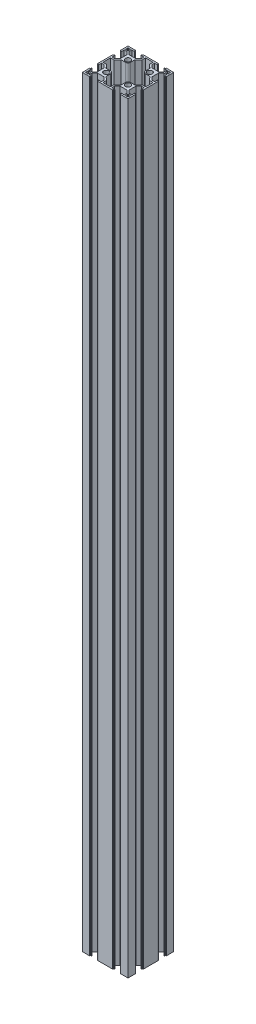
SolidWorks part; units mm, degrees
ref_plane "Front Plane" through (0, 0, 0) normal (0, 0, 1) x (1, 0, 0)
ref_plane "Top Plane" through (0, 0, 0) normal (0, 1, 0) x (1, 0, 0)
ref_plane "Right Plane" through (0, 0, 0) normal (1, 0, 0) x (0, 0, -1)
sketch "Sketch1" plane through (0, 0, 0) normal (0, 1, 0) x (1, 0, 0)
  line L0 (0, 30) -> (0, -30) construction
  line L1 (-30, -30) -> (30, -30)
  line L2 (-30, -30) -> (-30, 30)
  line L3 (-30, 30) -> (30, 30)
  line L4 (30, -30) -> (30, 30)
  line L5 (-30, -30) -> (30, 30) construction
  line L6 (-30, 30) -> (30, -30) construction
  line L7 (-30, 0) -> (30, 0) construction
  line L8 (-23.05, -28) -> (-6.95, -28)
  line L9 (-6.95, -28) -> (-6.95, -24.4)
  line L10 (-6.95, -24.4) -> (-10.615, -20.8)
  line L11 (-10.615, -20.8) -> (-19.385, -20.8)
  line L12 (-19.385, -20.8) -> (-23.05, -24.4)
  line L13 (-23.05, -24.4) -> (-23.05, -28)
  line L14 (10.615, -20.8) -> (19.385, -20.8)
  line L15 (6.95, -24.4) -> (10.615, -20.8)
  line L16 (6.95, -28) -> (6.95, -24.4)
  line L17 (23.05, -28) -> (6.95, -28)
  line L18 (23.05, -24.4) -> (23.05, -28)
  line L19 (19.385, -20.8) -> (23.05, -24.4)
  line L20 (19.385, 20.8) -> (23.05, 24.4)
  line L21 (23.05, 24.4) -> (23.05, 28)
  line L22 (23.05, 28) -> (6.95, 28)
  line L23 (6.95, 28) -> (6.95, 24.4)
  line L24 (6.95, 24.4) -> (10.615, 20.8)
  line L25 (10.615, 20.8) -> (19.385, 20.8)
  line L26 (-23.05, 24.4) -> (-23.05, 28)
  line L27 (-19.385, 20.8) -> (-23.05, 24.4)
  line L28 (-10.615, 20.8) -> (-19.385, 20.8)
  line L29 (-6.95, 24.4) -> (-10.615, 20.8)
  line L30 (-6.95, 28) -> (-6.95, 24.4)
  line L31 (-23.05, 28) -> (-6.95, 28)
  line L32 (-20.8, 19.385) -> (-24.4, 23.05)
  line L33 (-24.4, 23.05) -> (-28, 23.05)
  line L34 (-28, 23.05) -> (-28, 6.95)
  line L35 (-28, 6.95) -> (-24.4, 6.95)
  line L36 (-24.4, 6.95) -> (-20.8, 10.615)
  line L37 (-20.8, 10.615) -> (-20.8, 19.385)
  line L38 (-24.4, -23.05) -> (-28, -23.05)
  line L39 (-20.8, -19.385) -> (-24.4, -23.05)
  line L40 (-20.8, -10.615) -> (-20.8, -19.385)
  line L41 (-24.4, -6.95) -> (-20.8, -10.615)
  line L42 (-28, -6.95) -> (-24.4, -6.95)
  line L43 (-28, -23.05) -> (-28, -6.95)
  line L44 (20.8, -19.385) -> (24.4, -23.05)
  line L45 (24.4, -23.05) -> (28, -23.05)
  line L46 (28, -23.05) -> (28, -6.95)
  line L47 (28, -6.95) -> (24.4, -6.95)
  line L48 (24.4, -6.95) -> (20.8, -10.615)
  line L49 (20.8, -10.615) -> (20.8, -19.385)
  line L50 (24.4, 23.05) -> (28, 23.05)
  line L51 (20.8, 19.385) -> (24.4, 23.05)
  line L52 (20.8, 10.615) -> (20.8, 19.385)
  line L53 (24.4, 6.95) -> (20.8, 10.615)
  line L54 (28, 6.95) -> (24.4, 6.95)
  line L55 (28, 23.05) -> (28, 6.95)
  point P0 (0, 0)
  dimension "D1" = 60
  dimension "D2" = 16.1
  dimension "D3" = 8.77
  dimension "D4" = 3.6
  dimension "D5" = 7.2
  dimension "D6" = 2
  dimension "D7" = 6.95
extrude "Boss-Extrude1" add sketch "Sketch1" along normal blind 1000
sketch "Sketch2" plane through (0, 1000, 0) normal (0, 1, 0) x (1, 0, 0)
  line L0 (-19.1, -28) -> (-19.1, -29)
  line L1 (-23.05, -28) -> (-6.95, -28) construction
  line L2 (-30, -30) -> (30, -30) construction
  line L3 (-10.9, -28) -> (-10.9, -29)
  line L4 (-10.9, -29) -> (-9.9, -29)
  line L5 (-9.9, -29) -> (-9.9, -30)
  line L6 (-19.1, -29) -> (-20.1, -29)
  line L7 (-20.1, -29) -> (-20.1, -30)
  line L8 (-19.1, -28) -> (-10.9, -28)
  line L9 (-20.1, -30) -> (-9.9, -30)
  dimension "D1" = 8.2
  dimension "D2" = 3.95
  dimension "D3" = 1
  dimension "D4" = 1
extrude "Cut-Extrude1" cut sketch "Sketch2" against normal through all
mirror "Mirror1" about plane through (0, 0, 0) normal (1, 0, 0) of "Cut-Extrude1"
ref_axis "Axis1" through (0, 1050, 0) along (0, -1, 0)
pattern_circular "CirPattern1" count 4 over 360 about axis through (0, 1050, 0) along (0, -1, 0) of "Cut-Extrude1", "Mirror1"
sketch "Sketch4" plane through (0, 1000, 0) normal (0, 1, 0) x (1, 0, 0)
  line L0 (19.385, 18.8) -> (9.797, 18.8) construction
  line L1 (-18.8, 18.8) -> (-18.8, 9.797)
  line L2 (18.8, -19.385) -> (18.8, -9.797) construction
  line L3 (28, 4.95) -> (28, -4.95)
  line L4 (-18.8, -9.797) -> (-18.8, -19.385) construction
  line L5 (4.95, -28) -> (-4.95, -28)
  line L6 (-9.797, 18.8) -> (-9.797, 13.197)
  line L7 (-28, -4.95) -> (-28, 4.95)
  line L8 (-18.8, 9.797) -> (-23.5611, 4.95)
  line L9 (-23.5611, 4.95) -> (-28, 4.95)
  line L10 (18.8, 18.8) -> (9.797, 18.8)
  line L11 (9.797, 18.8) -> (4.95, 23.5611)
  line L12 (4.95, 23.5611) -> (4.95, 28)
  line L13 (4.95, 28) -> (4.95, 28)
  line L14 (4.95, 28) -> (4.95, 28)
  line L15 (4.95, 28) -> (4.95, 28)
  line L16 (4.95, 28) -> (4.95, 28)
  line L17 (4.95, 28) -> (-4.95, 28)
  line L18 (-4.95, 28) -> (-4.95, 28)
  line L19 (-4.95, 28) -> (-4.95, 28)
  line L20 (-4.95, 28) -> (-4.95, 28)
  line L21 (-4.95, 28) -> (-4.95, 28)
  line L22 (-4.95, 28) -> (-4.95, 23.5611)
  line L23 (-4.95, 23.5611) -> (-9.797, 18.8)
  line L24 (-9.797, 18.8) -> (-18.8, 18.8)
  line L25 (28, 4.95) -> (23.5611, 4.95)
  line L26 (23.5611, 4.95) -> (18.8, 9.797)
  line L27 (18.8, 9.797) -> (18.8, 18.8)
  line L28 (18.8, -18.8) -> (18.8, -9.797)
  line L29 (18.8, -9.797) -> (23.5611, -4.95)
  line L30 (23.5611, -4.95) -> (28, -4.95)
  line L31 (4.95, -28) -> (4.95, -23.5611)
  line L32 (4.95, -23.5611) -> (9.797, -18.8)
  line L33 (9.797, -18.8) -> (18.8, -18.8)
  line L34 (-18.8, -18.8) -> (-9.797, -18.8)
  line L35 (-9.797, -18.8) -> (-4.95, -23.5611)
  line L36 (-4.95, -23.5611) -> (-4.95, -28)
  line L37 (-28, -4.95) -> (-23.5611, -4.95)
  line L38 (-23.5611, -4.95) -> (-18.8, -9.797)
  line L39 (-18.8, -9.797) -> (-18.8, -18.8)
  line L40 (-9.797, 18.8) -> (-19.385, 18.8) construction
  line L41 (-18.8, 19.385) -> (-18.8, 9.797) construction
  line L42 (18.8, 9.797) -> (18.8, 19.385) construction
  line L43 (9.797, -18.8) -> (19.385, -18.8) construction
  line L44 (-19.385, -18.8) -> (-9.797, -18.8) construction
  line L45 (-13.197, 9.797) -> (-18.8, 9.797)
  line L46 (9.797, 18.8) -> (9.797, 13.197)
  line L47 (13.197, 9.797) -> (18.8, 9.797)
  line L48 (-18.8, -9.797) -> (-13.197, -9.797)
  line L49 (-9.797, -13.197) -> (-9.797, -18.8)
  line L50 (9.797, -18.8) -> (9.797, -13.197)
  line L51 (13.197, -9.797) -> (18.8, -9.797)
  line L52 (-27.5, -28) -> (-24.9, -28)
  line L53 (24.9, -28) -> (27.5, -28)
  line L54 (24.4, -27.5) -> (24.4, -24.9)
  line L55 (24.9, -24.4) -> (27.5, -24.4)
  line L56 (28, -27.5) -> (28, -24.9)
  line L57 (24.4, -28) -> (28, -24.4) construction
  line L58 (24.4, -24.4) -> (28, -28) construction
  line L59 (-28, -24.9) -> (-28, -27.5)
  line L60 (-27.5, -24.4) -> (-24.9, -24.4)
  line L61 (-24.4, -24.9) -> (-24.4, -27.5)
  line L62 (-28, 27.5) -> (-28, 24.9)
  line L63 (-24.9, 28) -> (-27.5, 28)
  line L64 (-24.4, 27.5) -> (-24.4, 24.9)
  line L65 (-24.9, 24.4) -> (-27.5, 24.4)
  line L66 (27.5, 28) -> (24.9, 28)
  line L67 (28, 24.9) -> (28, 27.5)
  line L68 (27.5, 24.4) -> (24.9, 24.4)
  line L69 (24.4, 24.9) -> (24.4, 27.5)
  line L116 (28, 19.1) -> (29, 19.1)
  line L117 (29, 19.1) -> (29, 20.1)
  line L118 (29, 20.1) -> (30, 20.1)
  line L119 (30, 20.1) -> (30, 30)
  line L120 (30, 30) -> (20.1, 30)
  line L121 (20.1, 30) -> (20.1, 29)
  line L122 (20.1, 29) -> (19.1, 29)
  line L123 (19.1, 29) -> (19.1, 28)
  line L124 (19.1, 28) -> (23.05, 28)
  line L125 (23.05, 28) -> (23.05, 24.4)
  line L126 (23.05, 24.4) -> (19.385, 20.8)
  line L127 (19.385, 20.8) -> (10.615, 20.8)
  line L128 (10.615, 20.8) -> (6.95, 24.4)
  line L129 (6.95, 24.4) -> (6.95, 28)
  line L130 (6.95, 28) -> (10.9, 28)
  line L131 (10.9, 28) -> (10.9, 29)
  line L132 (10.9, 29) -> (9.9, 29)
  line L133 (9.9, 29) -> (9.9, 30)
  line L134 (9.9, 30) -> (-9.9, 30)
  line L135 (-9.9, 30) -> (-9.9, 29)
  line L136 (-9.9, 29) -> (-10.9, 29)
  line L137 (-10.9, 29) -> (-10.9, 28)
  line L138 (-10.9, 28) -> (-6.95, 28)
  line L139 (-6.95, 28) -> (-6.95, 24.4)
  line L140 (-6.95, 24.4) -> (-10.615, 20.8)
  line L141 (-10.615, 20.8) -> (-19.385, 20.8)
  line L142 (-19.385, 20.8) -> (-23.05, 24.4)
  line L143 (-23.05, 24.4) -> (-23.05, 28)
  line L144 (-23.05, 28) -> (-19.1, 28)
  line L145 (-19.1, 28) -> (-19.1, 29)
  line L146 (-19.1, 29) -> (-20.1, 29)
  line L147 (-20.1, 29) -> (-20.1, 30)
  line L148 (-20.1, 30) -> (-30, 30)
  line L149 (-30, 30) -> (-30, 20.1)
  line L150 (-30, 20.1) -> (-29, 20.1)
  line L151 (-29, 20.1) -> (-29, 19.1)
  line L152 (-29, 19.1) -> (-28, 19.1)
  line L153 (-28, 19.1) -> (-28, 23.05)
  line L154 (-28, 23.05) -> (-24.4, 23.05)
  line L155 (-24.4, 23.05) -> (-20.8, 19.385)
  line L156 (-20.8, 19.385) -> (-20.8, 10.615)
  line L157 (-20.8, 10.615) -> (-24.4, 6.95)
  line L158 (-24.4, 6.95) -> (-28, 6.95)
  line L159 (-28, 6.95) -> (-28, 10.9)
  line L160 (-28, 10.9) -> (-29, 10.9)
  line L161 (-29, 10.9) -> (-29, 9.9)
  line L162 (-29, 9.9) -> (-30, 9.9)
  line L163 (-30, 9.9) -> (-30, -9.9)
  line L164 (-30, -9.9) -> (-29, -9.9)
  line L165 (-29, -9.9) -> (-29, -10.9)
  line L166 (-29, -10.9) -> (-28, -10.9)
  line L167 (-28, -10.9) -> (-28, -6.95)
  line L168 (-28, -6.95) -> (-24.4, -6.95)
  line L169 (-24.4, -6.95) -> (-20.8, -10.615)
  line L170 (-20.8, -10.615) -> (-20.8, -19.385)
  line L171 (-20.8, -19.385) -> (-24.4, -23.05)
  line L172 (-24.4, -23.05) -> (-28, -23.05)
  line L173 (-28, -23.05) -> (-28, -19.1)
  line L174 (-28, -19.1) -> (-29, -19.1)
  line L175 (-29, -19.1) -> (-29, -20.1)
  line L176 (-29, -20.1) -> (-30, -20.1)
  line L177 (-30, -20.1) -> (-30, -30)
  line L178 (-30, -30) -> (-20.1, -30)
  line L179 (-20.1, -30) -> (-20.1, -29)
  line L180 (-20.1, -29) -> (-19.1, -29)
  line L181 (-19.1, -29) -> (-19.1, -28)
  line L182 (-19.1, -28) -> (-23.05, -28)
  line L183 (-23.05, -28) -> (-23.05, -24.4)
  line L184 (-23.05, -24.4) -> (-19.385, -20.8)
  line L185 (-19.385, -20.8) -> (-10.615, -20.8)
  line L186 (-10.615, -20.8) -> (-6.95, -24.4)
  line L187 (-6.95, -24.4) -> (-6.95, -28)
  line L188 (-6.95, -28) -> (-10.9, -28)
  line L189 (-10.9, -28) -> (-10.9, -29)
  line L190 (-10.9, -29) -> (-9.9, -29)
  line L191 (-9.9, -29) -> (-9.9, -30)
  line L192 (-9.9, -30) -> (9.9, -30)
  line L193 (9.9, -30) -> (9.9, -29)
  line L194 (9.9, -29) -> (10.9, -29)
  line L195 (10.9, -29) -> (10.9, -28)
  line L196 (10.9, -28) -> (6.95, -28)
  line L197 (6.95, -28) -> (6.95, -24.4)
  line L198 (6.95, -24.4) -> (10.615, -20.8)
  line L199 (10.615, -20.8) -> (19.385, -20.8)
  line L200 (19.385, -20.8) -> (23.05, -24.4)
  line L201 (23.05, -24.4) -> (23.05, -28)
  line L202 (23.05, -28) -> (19.1, -28)
  line L203 (19.1, -28) -> (19.1, -29)
  line L204 (19.1, -29) -> (20.1, -29)
  line L205 (20.1, -29) -> (20.1, -30)
  line L206 (20.1, -30) -> (30, -30)
  line L207 (30, -30) -> (30, -20.1)
  line L208 (30, -20.1) -> (29, -20.1)
  line L209 (29, -20.1) -> (29, -19.1)
  line L210 (29, -19.1) -> (28, -19.1)
  line L211 (28, -19.1) -> (28, -23.05)
  line L212 (28, -23.05) -> (24.4, -23.05)
  line L213 (24.4, -23.05) -> (20.8, -19.385)
  line L214 (20.8, -19.385) -> (20.8, -10.615)
  line L215 (20.8, -10.615) -> (24.4, -6.95)
  line L216 (24.4, -6.95) -> (28, -6.95)
  line L217 (28, -6.95) -> (28, -10.9)
  line L218 (28, -10.9) -> (29, -10.9)
  line L219 (29, -10.9) -> (29, -9.9)
  line L220 (29, -9.9) -> (30, -9.9)
  line L221 (30, -9.9) -> (30, 9.9)
  line L222 (30, 9.9) -> (29, 9.9)
  line L223 (29, 9.9) -> (29, 10.9)
  line L224 (29, 10.9) -> (28, 10.9)
  line L225 (28, 10.9) -> (28, 6.95)
  line L226 (28, 6.95) -> (24.4, 6.95)
  line L227 (24.4, 6.95) -> (20.8, 10.615)
  line L228 (20.8, 10.615) -> (20.8, 19.385)
  line L229 (20.8, 19.385) -> (24.4, 23.05)
  line L230 (24.4, 23.05) -> (28, 23.05)
  line L231 (28, 23.05) -> (28, 19.1)
  line L232 (28, 19.1) -> (29, 19.1)
  line L233 (29, 19.1) -> (29, 20.1)
  line L234 (29, 20.1) -> (30, 20.1)
  line L235 (30, 20.1) -> (30, 30)
  line L236 (30, 30) -> (20.1, 30)
  line L237 (20.1, 30) -> (20.1, 29)
  line L238 (20.1, 29) -> (19.1, 29)
  line L239 (19.1, 29) -> (19.1, 28)
  line L240 (19.1, 28) -> (23.05, 28)
  line L241 (23.05, 28) -> (23.05, 24.4)
  line L242 (23.05, 24.4) -> (19.385, 20.8)
  line L243 (19.385, 20.8) -> (10.615, 20.8)
  line L244 (10.615, 20.8) -> (6.95, 24.4)
  line L245 (6.95, 24.4) -> (6.95, 28)
  line L246 (6.95, 28) -> (10.9, 28)
  line L247 (10.9, 28) -> (10.9, 29)
  line L248 (10.9, 29) -> (9.9, 29)
  line L249 (9.9, 29) -> (9.9, 30)
  line L250 (9.9, 30) -> (-9.9, 30)
  line L251 (-9.9, 30) -> (-9.9, 29)
  line L252 (-9.9, 29) -> (-10.9, 29)
  line L253 (-10.9, 29) -> (-10.9, 28)
  line L254 (-10.9, 28) -> (-6.95, 28)
  line L255 (-6.95, 28) -> (-6.95, 24.4)
  line L256 (-6.95, 24.4) -> (-10.615, 20.8)
  line L257 (-10.615, 20.8) -> (-19.385, 20.8)
  line L258 (-19.385, 20.8) -> (-23.05, 24.4)
  line L259 (-23.05, 24.4) -> (-23.05, 28)
  line L260 (-23.05, 28) -> (-19.1, 28)
  line L261 (-19.1, 28) -> (-19.1, 29)
  line L262 (-19.1, 29) -> (-20.1, 29)
  line L263 (-20.1, 29) -> (-20.1, 30)
  line L264 (-20.1, 30) -> (-30, 30)
  line L265 (-30, 30) -> (-30, 20.1)
  line L266 (-30, 20.1) -> (-29, 20.1)
  line L267 (-29, 20.1) -> (-29, 19.1)
  line L268 (-29, 19.1) -> (-28, 19.1)
  line L269 (-28, 19.1) -> (-28, 23.05)
  line L270 (-28, 23.05) -> (-24.4, 23.05)
  line L271 (-24.4, 23.05) -> (-20.8, 19.385)
  line L272 (-20.8, 19.385) -> (-20.8, 10.615)
  line L273 (-20.8, 10.615) -> (-24.4, 6.95)
  line L274 (-24.4, 6.95) -> (-28, 6.95)
  line L275 (-28, 6.95) -> (-28, 10.9)
  line L276 (-28, 10.9) -> (-29, 10.9)
  line L277 (-29, 10.9) -> (-29, 9.9)
  line L278 (-29, 9.9) -> (-30, 9.9)
  line L279 (-30, 9.9) -> (-30, -9.9)
  line L280 (-30, -9.9) -> (-29, -9.9)
  line L281 (-29, -9.9) -> (-29, -10.9)
  line L282 (-29, -10.9) -> (-28, -10.9)
  line L283 (-28, -10.9) -> (-28, -6.95)
  line L284 (-28, -6.95) -> (-24.4, -6.95)
  line L285 (-24.4, -6.95) -> (-20.8, -10.615)
  line L286 (-20.8, -10.615) -> (-20.8, -19.385)
  line L287 (-20.8, -19.385) -> (-24.4, -23.05)
  line L288 (-24.4, -23.05) -> (-28, -23.05)
  line L289 (-28, -23.05) -> (-28, -19.1)
  line L290 (-28, -19.1) -> (-29, -19.1)
  line L291 (-29, -19.1) -> (-29, -20.1)
  line L292 (-29, -20.1) -> (-30, -20.1)
  line L293 (-30, -20.1) -> (-30, -30)
  line L294 (-30, -30) -> (-20.1, -30)
  line L295 (-20.1, -30) -> (-20.1, -29)
  line L296 (-20.1, -29) -> (-19.1, -29)
  line L297 (-19.1, -29) -> (-19.1, -28)
  line L298 (-19.1, -28) -> (-23.05, -28)
  line L299 (-23.05, -28) -> (-23.05, -24.4)
  line L300 (-23.05, -24.4) -> (-19.385, -20.8)
  line L301 (-19.385, -20.8) -> (-10.615, -20.8)
  line L302 (-10.615, -20.8) -> (-6.95, -24.4)
  line L303 (-6.95, -24.4) -> (-6.95, -28)
  line L304 (-6.95, -28) -> (-10.9, -28)
  line L305 (-10.9, -28) -> (-10.9, -29)
  line L306 (-10.9, -29) -> (-9.9, -29)
  line L307 (-9.9, -29) -> (-9.9, -30)
  line L308 (-9.9, -30) -> (9.9, -30)
  line L309 (9.9, -30) -> (9.9, -29)
  line L310 (9.9, -29) -> (10.9, -29)
  line L311 (10.9, -29) -> (10.9, -28)
  line L312 (10.9, -28) -> (6.95, -28)
  line L313 (6.95, -28) -> (6.95, -24.4)
  line L314 (6.95, -24.4) -> (10.615, -20.8)
  line L315 (10.615, -20.8) -> (19.385, -20.8)
  line L316 (19.385, -20.8) -> (23.05, -24.4)
  line L317 (23.05, -24.4) -> (23.05, -28)
  line L318 (23.05, -28) -> (19.1, -28)
  line L319 (19.1, -28) -> (19.1, -29)
  line L320 (19.1, -29) -> (20.1, -29)
  line L321 (20.1, -29) -> (20.1, -30)
  line L322 (20.1, -30) -> (30, -30)
  line L323 (30, -30) -> (30, -20.1)
  line L324 (30, -20.1) -> (29, -20.1)
  line L325 (29, -20.1) -> (29, -19.1)
  line L326 (29, -19.1) -> (28, -19.1)
  line L327 (28, -19.1) -> (28, -23.05)
  line L328 (28, -23.05) -> (24.4, -23.05)
  line L329 (24.4, -23.05) -> (20.8, -19.385)
  line L330 (20.8, -19.385) -> (20.8, -10.615)
  line L331 (20.8, -10.615) -> (24.4, -6.95)
  line L332 (24.4, -6.95) -> (28, -6.95)
  line L333 (28, -6.95) -> (28, -10.9)
  line L334 (28, -10.9) -> (29, -10.9)
  line L335 (29, -10.9) -> (29, -9.9)
  line L336 (29, -9.9) -> (30, -9.9)
  line L337 (30, -9.9) -> (30, 9.9)
  line L338 (30, 9.9) -> (29, 9.9)
  line L339 (29, 9.9) -> (29, 10.9)
  line L340 (29, 10.9) -> (28, 10.9)
  line L341 (28, 10.9) -> (28, 6.95)
  line L342 (28, 6.95) -> (24.4, 6.95)
  line L343 (24.4, 6.95) -> (20.8, 10.615)
  line L344 (20.8, 10.615) -> (20.8, 19.385)
  line L345 (20.8, 19.385) -> (24.4, 23.05)
  line L346 (24.4, 23.05) -> (28, 23.05)
  line L347 (28, 23.05) -> (28, 19.1)
  circle A0 centre (14.2985, 14.2985) radius 3.4
  arc A1 (13.197, -9.797) -> (9.797, -13.197) centre (13.197, -13.197) ccw
  arc A2 (-9.797, -13.197) -> (-13.197, -9.797) centre (-13.197, -13.197) ccw
  arc A3 (13.197, 9.797) -> (9.797, 13.197) centre (13.197, 13.197) cw
  arc A4 (-9.797, 13.197) -> (-13.197, 9.797) centre (-13.197, 13.197) cw
  circle A5 centre (14.2985, -14.2985) radius 3.4
  circle A6 centre (-14.2985, -14.2985) radius 3.4
  circle A7 centre (-14.2985, 14.2985) radius 3.4
  arc A8 (24.4, -27.5) -> (24.9, -28) centre (24.9, -27.5) ccw
  arc A9 (28, -27.5) -> (27.5, -28) centre (27.5, -27.5) cw
  arc A10 (28, -24.9) -> (27.5, -24.4) centre (27.5, -24.9) ccw
  arc A11 (24.4, -24.9) -> (24.9, -24.4) centre (24.9, -24.9) cw
  arc A12 (-27.5, -28) -> (-28, -27.5) centre (-27.5, -27.5) cw
  arc A13 (-27.5, -24.4) -> (-28, -24.9) centre (-27.5, -24.9) ccw
  arc A14 (-24.9, -24.4) -> (-24.4, -24.9) centre (-24.9, -24.9) cw
  arc A15 (-24.9, -28) -> (-24.4, -27.5) centre (-24.9, -27.5) ccw
  arc A16 (-28, 27.5) -> (-27.5, 28) centre (-27.5, 27.5) cw
  arc A17 (-24.4, 27.5) -> (-24.9, 28) centre (-24.9, 27.5) ccw
  arc A18 (-24.4, 24.9) -> (-24.9, 24.4) centre (-24.9, 24.9) cw
  arc A19 (-28, 24.9) -> (-27.5, 24.4) centre (-27.5, 24.9) ccw
  arc A20 (27.5, 28) -> (28, 27.5) centre (27.5, 27.5) cw
  arc A21 (27.5, 24.4) -> (28, 24.9) centre (27.5, 24.9) ccw
  arc A22 (24.9, 24.4) -> (24.4, 24.9) centre (24.9, 24.9) cw
  arc A23 (24.9, 28) -> (24.4, 27.5) centre (24.9, 27.5) ccw
  point P102 (26.2, -26.2)
  point P104 (14.2985, 18.8)
  point P106 (18.8, 14.2985)
  point P140 (0, 0)
  point P239 (0, 0)
  dimension "D3" = 6.8
  dimension "D4" = 3.4
  dimension "D6" = 0.5
  dimension "D1" = 0
  dimension "D2" = 2
  dimension "D5" = 4
  dimension "D7" = 4
extrude "Cut-Extrude2" cut sketch "Sketch4" against normal blind 1000 contours L6 A4 L45 L8 L9 L7 L37 L38 L48 A2 L49 L35 L36 L5 L31 L32 L50 A1 L51 L29 L30 L3 L25 L26 L47 A3 L46 L11 L12 L17 L22 L23 | A7 | A0 | L66 A23 L69 A22 L68 A21 L67 A20 | L62 A19 L65 A18 L64 A17 L63 A16 | L52 A15 L61 A14 L60 A13 L59 A12 | A11 L54 A8 L53 A9 L56 A10 L55 | A6 | A5 region at (0, 1000, 0) region at (-26.2, 1000, 26.2) region at (26.2, 1000, 26.2) region at (-26.2, 1000, -26.2) region at (26.2, 1000, -26.2) region at (14.2985, 1000, -14.2985) region at (-14.2985, 1000, -14.2985)
fillet "Fillet1" radius 0.2 16 edges at (28, 500, -19.1) (30, 500, -20.1) (29, 500, -20.1) (29, 500, -19.1) (28, 500, 10.9) (29, 500, 9.9) (28, 500, 19.1) (29, 500, 20.1) (30, 500, 20.1) (29, 500, 19.1) (29, 500, 10.9) (30, 500, 9.9) (30, 500, -9.9) (29, 500, -9.9) (29, 500, -10.9) (28, 500, -10.9)
fillet "Fillet2" radius 0.2 20 edges at (-20.1, 0, -29.5) (-20.1, 1000, -29.5) (-20.1, 500, -29) (-19.6, 0, -29) (-19.1, 500, -29) (-19.6, 1000, -29) (-9.9, 500, -30) (-10.9, 500, -28) (-10.9, 500, -29) (-9.9, 500, -29) (19.1, 500, -28) (19.1, 500, -29) (20.1, 500, -29) (20.1, 500, -30) (10.9, 500, -28) (10.9, 500, -29) (9.9, 500, -29) (9.9, 500, -30) (-19.1, 500, -28) (-20.1, 500, -30)
fillet "Fillet3" radius 0.2 14 edges at (-29, 500, 9.9) (-29, 500, -20.1) (-30, 500, -20.1) (-29, 500, -19.1) (-28, 500, -10.9) (-29, 500, -10.9) (-29, 500, -9.9) (-30, 500, -9.9) (-29, 500, 10.9) (-30, 500, 9.9) (-28, 500, 19.1) (-29, 500, 19.1) (-29, 500, 20.1) (-30, 500, 20.1)
fillet "Fillet4" radius 0.2 16 edges at (-19.1, 500, 28) (10.9, 500, 28) (19.1, 500, 28) (20.1, 500, 29) (-10.9, 500, 28) (-9.9, 500, 29) (9.9, 500, 29) (-20.1, 500, 29) (19.1, 500, 29) (20.1, 500, 30) (10.9, 500, 29) (9.9, 500, 30) (-9.9, 500, 30) (-10.9, 500, 29) (-19.1, 500, 29) (-20.1, 500, 30)
